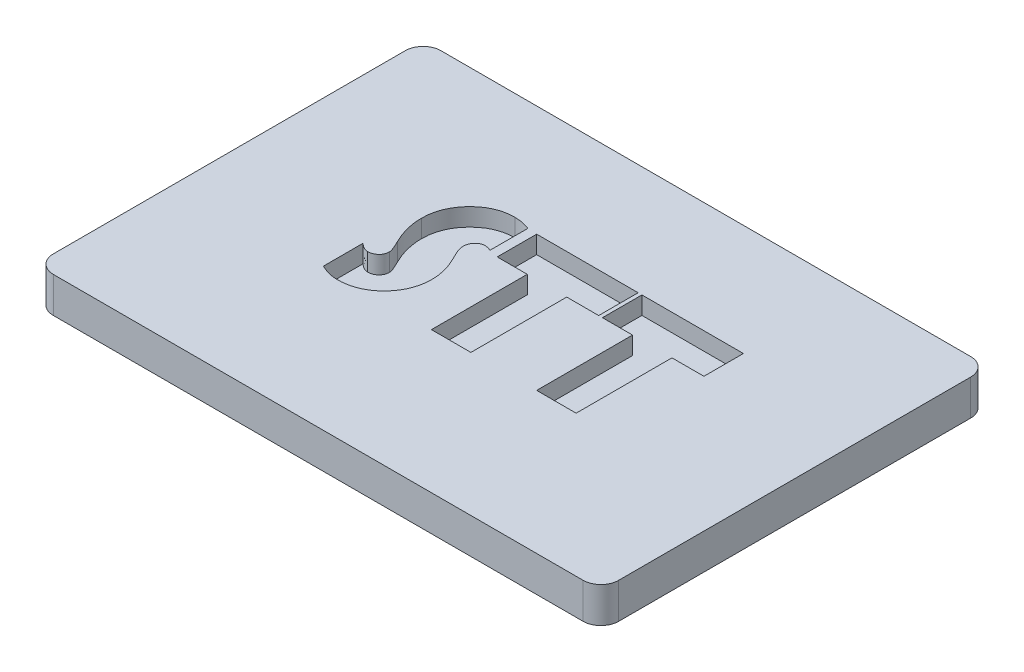
SolidWorks part; units mm, degrees
ref_plane "Front Plane" through (0, 0, 0) normal (0, 0, 1) x (1, 0, 0)
ref_plane "Top Plane" through (0, 0, 0) normal (0, 1, 0) x (1, 0, 0)
ref_plane "Right Plane" through (0, 0, 0) normal (1, 0, 0) x (0, 0, -1)
sketch "Sketch1" plane through (0, 0, 0) normal (0, 1, 0) x (1, 0, 0)
  line L1 (0, 0) -> (31.8, 0)
  line L2 (0, 0) -> (0, 21.8)
  line L3 (0, 21.8) -> (31.8, 21.8)
  line L4 (31.8, 0) -> (31.8, 21.8)
  dimension "D1" = 21.8
  dimension "D2" = 31.8
extrude "Boss-Extrude1" add sketch "Sketch1" along normal blind 2
fillet "Fillet1" radius 1 4 edges at (0, 1, -21.8) (31.8, 1, -21.8) (31.8, 1, 0) (0, 1, 0)
sketch "Sketch2" plane through (0, 2, 0) normal (0, 1, 0) x (1, 0, 0)
  text T0 "STT" font "Bauhaus 93" height in points 24
extrude "Cut-Extrude1" cut sketch "Sketch2" against normal blind 1
